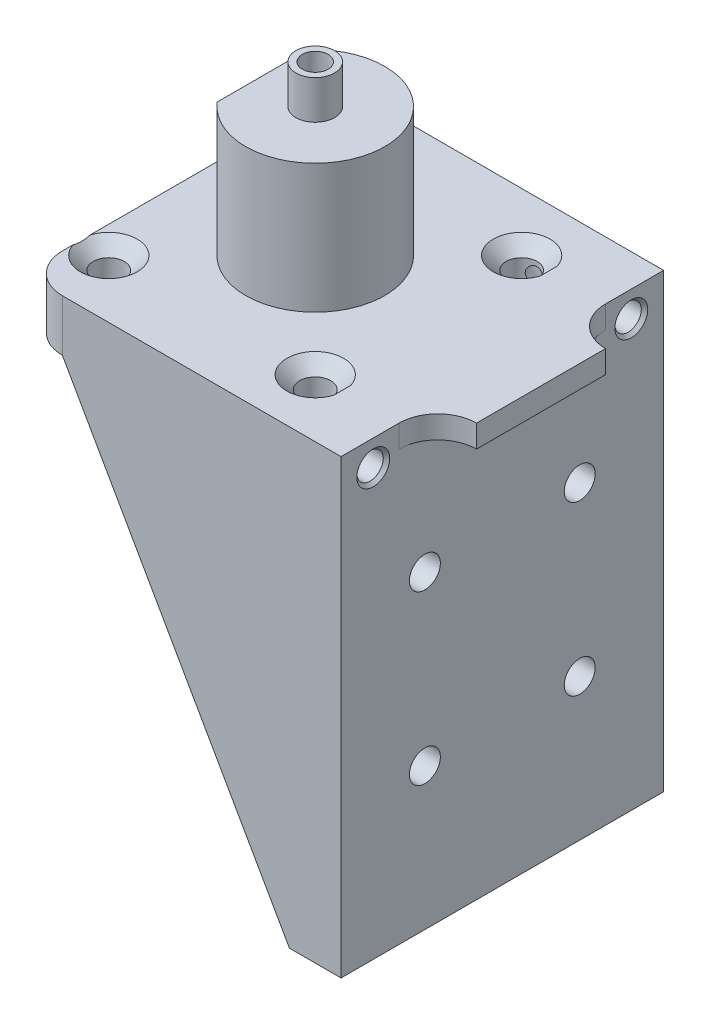
SolidWorks part; units mm, degrees
material "PA Тип 6"
ref_plane "Front" through (0, 0, 0) normal (0, 0, 1) x (1, 0, 0)
ref_plane "Top" through (0, 0, 0) normal (0, 1, 0) x (1, 0, 0)
ref_plane "Right" through (0, 0, 0) normal (1, 0, 0) x (0, 0, -1)
sketch "Model" plane through (0, 0, 0) normal (0, 1, 0) x (1, 0, 0)
  line L1 (-10.1, 12.5) -> (10.1, 12.5)
  line L2 (-10.1, 12.5) -> (-10.1, -12.5)
  line L3 (-10.1, -12.5) -> (10.1, -12.5)
  line L8 (10.1, 12.5) -> (10.1, -12.5)
  line L9 (-10.1, 12.5) -> (10.1, -12.5) construction
  line L10 (-10.1, -12.5) -> (10.1, 12.5) construction
  point P0 (0, 0)
  dimension "D1" = 25
  dimension "D4" = 20.2
extrude "База" add sketch "Model" along normal blind 4
hole_wizard "Крепление М2" positions "Эскиз9" profile "Эскиз11" countersink size "M2" standard "DIN" end condition through all
sketch "Эскиз9" plane through (0, 4, 0) normal (0, 1, 0) x (1, 0, 0)
  line L0 (-8, 8) -> (0, 8) construction
  line L1 (0, 8) -> (8, 8) construction
  line L2 (8, 8) -> (8, 0) construction
  line L3 (8, 0) -> (8, -8) construction
  point P0 (-8, 8)
  point P2 (8, 8)
  point P4 (8, -8)
  point P6 (-8, -8)
  dimension "D1" = 16
sketch "Эскиз11" plane through (-8, 4, -8) normal (1, 0, 0) x (0, 0, 1)
  line L0 (0, 0) -> (0, 4)
  line L1 (0, 4) -> (1.2, 4)
  line L2 (1.2, 4) -> (1.2, 1)
  line L3 (1.2, 1) -> (2.2, 0)
  line L5 (2.2, 0) -> (0, 0)
  line L6 (-1.2, 1) -> (-2.2, 0) construction
  line L11 (0, -6.35) -> (0, 107.95) construction
  dimension "Диаметр сквозного отверстия" = 2.4
  dimension "Глубина сквозного отверстия" = 4
  dimension "Диаметр передней зенковки" = 4.4
  dimension "Угол передней зенковки" = 90
sketch "Эскиз12" plane through (10.1, 0, 0) normal (1, 0, 0) x (0, 0, -1)
  line L1 (-12.5, 4) -> (12.5, 4)
  line L2 (-12.5, 4) -> (-12.5, 0)
  line L3 (-12.5, 0) -> (12.5, 0)
  line L4 (12.5, 4) -> (12.5, 0)
extrude "Бобышка-Вытянуть4" add sketch "Эскиз12" along normal blind 0.4
sketch "Эскиз13" plane through (10.5, 0, 0) normal (1, 0, 0) x (0, 0, -1)
  line L1 (-12.5, 4) -> (12.5, 4)
  line L2 (-12.5, 4) -> (-12.5, -31)
  line L3 (-12.5, -31) -> (12.5, -31)
  line L4 (12.5, 4) -> (12.5, -31)
  line L6 (12.5, 4) -> (-12.5, 4) construction
  point P4 (0, 4)
  dimension "D2" = 35
extrude "Бобышка-Вытянуть5" add sketch "Эскиз13" along normal blind 4
fillet "Скругление1" radius 3 2 edges at (-10.1, 2, -12.5) (-10.1, 2, 12.5)
sketch "Эскиз15" plane through (0, 0, 12.5) normal (0, 0, 1) x (1, 0, 0)
  line L0 (-7.1, 0) -> (10.5, 0)
  line L1 (10.5, 0) -> (10.5, -31)
  line L2 (10.5, 0) -> (10.5, -31) construction
  line L3 (10.5, -31) -> (-7.1, 0)
extrude "Усиление" add sketch "Эскиз15" against normal blind 2
mirror "Зеркальное отражение1" about plane through (0, 0, 0) normal (0, 0, 1) of "Усиление"
sketch "Эскиз16" plane through (0, 0, 0) normal (0, -1, 0) x (1, 0, 0)
  circle A0 centre (0, 0) radius 7.5
  dimension "D1" = 15
extrude "Вырез-Вытянуть5" cut sketch "Эскиз16" against normal blind 1.5
hole_wizard "Зенковка для винта с полупотайной головкой M21" positions "Эскиз17" profile "Эскиз18" countersink size "M2" standard "DIN" end condition through all
sketch "Эскиз17" plane through (10.5, 0, 0) normal (-1, 0, 0) x (0, 0, 1)
  line L0 (-6, -7) -> (0, -7) construction
  line L1 (0, -7) -> (6, -7) construction
  point P0 (-6, -7)
  point P2 (6, -7)
  point P4 (6, -20)
  point P6 (-6, -20)
  dimension "D1" = 12
  dimension "D2" = 13
  dimension "D3" = 7
sketch "Эскиз18" plane through (10.5, -7, -6) normal (0, 1, 0) x (0, 0, 1)
  line L0 (0, 0) -> (0, 4)
  line L1 (0, 4) -> (1.2, 4)
  line L2 (1.2, 4) -> (1.2, 1)
  line L3 (1.2, 1) -> (2.2, 0)
  line L5 (2.2, 0) -> (0, 0)
  line L6 (-1.2, 1) -> (-2.2, 0) construction
  line L11 (0, -6.35) -> (0, 107.95) construction
  dimension "Диаметр сквозного отверстия" = 2.4
  dimension "Глубина сквозного отверстия" = 4
  dimension "Диаметр передней зенковки" = 4.4
  dimension "Угол передней зенковки" = 90
sketch "Эскиз23" plane through (14.5, 0, 0) normal (1, 0, 0) x (0, 0, -1)
  line L0 (12.5, 4) -> (-12.5, 4) construction
  line L1 (-5, 4) -> (5, 4)
  line L2 (-5, 4) -> (-5, 2.25)
  line L3 (-5, 2.25) -> (5, 2.25)
  line L4 (5, 4) -> (5, 2.25)
  point P6 (0, 4)
  point P7 (0, 4)
  dimension "D1" = 10
  dimension "D2" = 1.75
extrude "Стопор" add sketch "Эскиз23" along normal blind 3
fillet "Скругление5" radius 3 4 edges at (10.5, -15.5, 10.5) (10.5, -15.5, -10.5) (14.5, 3.125, -5) (14.5, 3.125, 5)
hole_wizard "Пружина-M2.5" positions "Эскиз21" profile "Эскиз22" tap size "M2.5" standard "DIN"
sketch "Эскиз21" plane through (14.5, 8, 27) normal (-1, 0, 0) x (0, 0, -1)
  line L7 (14.5, 4) -> (14.5, 8) construction
  line L9 (37, 6) -> (39.5, 6) construction
  line L10 (39.5, 39) -> (39.5, 4) construction
  line L13 (17, 6) -> (14.5, 6) construction
  line L14 (14.5, 4) -> (14.5, 39) construction
  point P0 (17, 6)
  point P23 (14.5, 6)
  point P28 (37, 6)
  dimension "D1" = 2.5
cosmetic thread "Отверстие резьбы2" parameters "D1"=5, "D2"=2.5
cosmetic thread "Отверстие резьбы3" parameters "D1"=5, "D2"=2.5
sketch "Эскиз22" plane through (14.5, 2, 10) normal (0, 1, 0) x (0, 0, -1)
  line L0 (0, 0) -> (0, 7.8659)
  line L1 (0, 7.8659) -> (1.025, 7.25)
  line L2 (1.025, 7.25) -> (1.025, 0.25)
  line L3 (1.025, 0.25) -> (1.275, 0)
  line L5 (1.275, 0) -> (0, 0)
  line L6 (-1.025, 0.25) -> (-1.275, 0) construction
  line L10 (0, 7.8659) -> (-1.025, 7.25) construction
  line L11 (0, -6.35) -> (0, 107.95) construction
  dimension "Диаметр сверла" = 2.05
  dimension "Глубина сверла" = 7.25
  dimension "Диаметр передней зенковки" = 2.55
  dimension "Угол передней зенковки" = 90
  dimension "Угол заточки сверла" = 118
sketch "Эскиз2" plane through (0, 4, 0) normal (0, 1, 0) x (1, 0, 0)
  line L11 (-4.1, 3.5) -> (-4.1, -3.5)
  line L12 (-10.1, 7.3443) -> (-10.1, -7.3443) construction
  arc A2 (-4.1, 3.5) -> (-4.1, -3.5) centre (0, 0) cw
  dimension "D2" = 6
  dimension "D1" = 7
extrude "БазаВакуумнойМагистрали" add sketch "Эскиз2" along normal blind 10
sketch "Эскиз4" plane through (0, 14, 0) normal (0, 1, 0) x (1, 0, 0)
  circle A0 centre (0, 0) radius 1.5
  dimension "D2" = 3
extrude "Шланг" add sketch "Эскиз4" along normal blind 3
sketch "Эскиз6" plane through (0, 17, 0) normal (0, 1, 0) x (1, 0, 0)
  circle A0 centre (0, 0) radius 1
  dimension "D1" = 2
extrude "ШлангID" cut sketch "Эскиз6" against normal through all
sketch "Эскиз5" plane through (0, 0, 0) normal (0, -1, 0) x (1, 0, 0)
  circle A0 centre (0, 0) radius 2.525
  dimension "D1" = 5.05
extrude "Вал-5mm" cut sketch "Эскиз5" against normal blind 12
sketch "Эскиз3" plane through (-4.1, 0, -1) normal (1, 0, 0) x (0, 0, -1)
  line L2 (2.5, 14) -> (-4.5, 14) construction
  circle A0 centre (-1, 10.5) radius 1.5
  dimension "D1" = 3
  dimension "D2" = 3.5
extrude "Датчик" cut sketch "Эскиз3" along normal up to surface (2.0688 mm away) up to face at (0, 1.5, -2.525)
